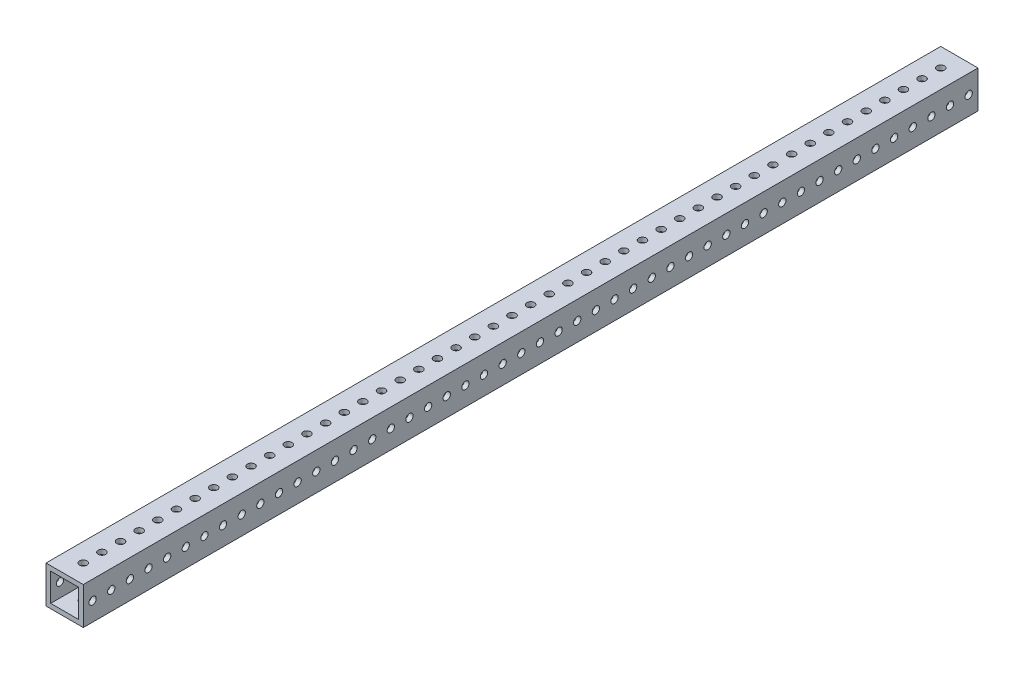
SolidWorks part; units mm, degrees
material "6061-T6 (SS)"
ref_plane "Front Plane" through (0, 0, 0) normal (0, 0, 1) x (1, 0, 0)
ref_plane "Top Plane" through (0, 0, 0) normal (0, 1, 0) x (1, 0, 0)
ref_plane "Right Plane" through (0, 0, 0) normal (1, 0, 0) x (0, 0, -1)
sketch "Sketch1" plane through (0, 0, 0) normal (0, 0, 1) x (1, 0, 0)
  line L0 (-9.525, 9.525) -> (9.525, 9.525)
  line L1 (-12.7, 12.7) -> (12.7, 12.7)
  line L2 (-12.7, 12.7) -> (-12.7, -12.7)
  line L3 (-12.7, -12.7) -> (12.7, -12.7)
  line L4 (12.7, 12.7) -> (12.7, -12.7)
  line L5 (9.525, 9.525) -> (9.525, -9.525)
  line L6 (-9.525, -9.525) -> (9.525, -9.525)
  line L7 (-9.525, 9.525) -> (-9.525, -9.525)
  line L8 (-12.7, 12.7) -> (12.7, -12.7) construction
  line L9 (12.7, 12.7) -> (-12.7, -12.7) construction
  point P5 (0, 0)
  dimension "D1" = 25.4
  dimension "D2" = 25.4
  dimension "D3" = 3.175
extrude "Boss-Extrude1" add sketch "Sketch1" along normal mid plane 609.6
sketch "Sketch2" plane through (0, 12.7, 0) normal (0, 1, 0) x (1, 0, 0)
  line L0 (12.7, -304.8) -> (-12.7, -304.8) construction
  line L1 (-12.7, -304.8) -> (-12.7, 304.8) construction
  line L4 (12.7, 304.8) -> (-12.7, 304.8) construction
  circle A0 centre (12.7, -292.1) radius 2.5527 construction
  circle A1 centre (25.4, -292.1) radius 2.5527 construction
  circle A2 centre (0, -292.1) radius 2.5527
  circle A3 centre (0, -279.4) radius 2.5527
  circle A4 centre (12.7, -279.4) radius 2.5527 construction
  circle A5 centre (25.4, -279.4) radius 2.5527 construction
  circle A6 centre (0, -266.7) radius 2.5527
  circle A7 centre (12.7, -266.7) radius 2.5527 construction
  circle A8 centre (25.4, -266.7) radius 2.5527 construction
  circle A9 centre (0, -254) radius 2.5527
  circle A10 centre (12.7, -254) radius 2.5527 construction
  circle A11 centre (25.4, -254) radius 2.5527 construction
  circle A12 centre (0, -241.3) radius 2.5527
  circle A13 centre (12.7, -241.3) radius 2.5527 construction
  circle A14 centre (25.4, -241.3) radius 2.5527 construction
  circle A15 centre (0, -228.6) radius 2.5527
  circle A16 centre (12.7, -228.6) radius 2.5527 construction
  circle A17 centre (25.4, -228.6) radius 2.5527 construction
  circle A18 centre (0, -215.9) radius 2.5527
  circle A19 centre (12.7, -215.9) radius 2.5527 construction
  circle A20 centre (25.4, -215.9) radius 2.5527 construction
  circle A21 centre (0, -203.2) radius 2.5527
  circle A22 centre (12.7, -203.2) radius 2.5527 construction
  circle A23 centre (25.4, -203.2) radius 2.5527 construction
  circle A24 centre (0, -190.5) radius 2.5527
  circle A25 centre (12.7, -190.5) radius 2.5527 construction
  circle A26 centre (25.4, -190.5) radius 2.5527 construction
  circle A27 centre (0, -177.8) radius 2.5527
  circle A28 centre (12.7, -177.8) radius 2.5527 construction
  circle A29 centre (25.4, -177.8) radius 2.5527 construction
  circle A30 centre (0, -165.1) radius 2.5527
  circle A31 centre (12.7, -165.1) radius 2.5527 construction
  circle A32 centre (25.4, -165.1) radius 2.5527 construction
  circle A33 centre (0, -152.4) radius 2.5527
  circle A34 centre (12.7, -152.4) radius 2.5527 construction
  circle A35 centre (25.4, -152.4) radius 2.5527 construction
  circle A36 centre (0, -139.7) radius 2.5527
  circle A37 centre (12.7, -139.7) radius 2.5527 construction
  circle A38 centre (25.4, -139.7) radius 2.5527 construction
  circle A39 centre (0, -127) radius 2.5527
  circle A40 centre (12.7, -127) radius 2.5527 construction
  circle A41 centre (25.4, -127) radius 2.5527 construction
  circle A42 centre (0, -114.3) radius 2.5527
  circle A43 centre (12.7, -114.3) radius 2.5527 construction
  circle A44 centre (25.4, -114.3) radius 2.5527 construction
  circle A45 centre (0, -101.6) radius 2.5527
  circle A46 centre (12.7, -101.6) radius 2.5527 construction
  circle A47 centre (25.4, -101.6) radius 2.5527 construction
  circle A48 centre (0, -88.9) radius 2.5527
  circle A49 centre (12.7, -88.9) radius 2.5527 construction
  circle A50 centre (25.4, -88.9) radius 2.5527 construction
  circle A51 centre (0, -76.2) radius 2.5527
  circle A52 centre (12.7, -76.2) radius 2.5527 construction
  circle A53 centre (25.4, -76.2) radius 2.5527 construction
  circle A54 centre (0, -63.5) radius 2.5527
  circle A55 centre (12.7, -63.5) radius 2.5527 construction
  circle A56 centre (25.4, -63.5) radius 2.5527 construction
  circle A57 centre (0, -50.8) radius 2.5527
  circle A58 centre (12.7, -50.8) radius 2.5527 construction
  circle A59 centre (25.4, -50.8) radius 2.5527 construction
  circle A60 centre (0, -38.1) radius 2.5527
  circle A61 centre (12.7, -38.1) radius 2.5527 construction
  circle A62 centre (25.4, -38.1) radius 2.5527 construction
  circle A63 centre (0, -25.4) radius 2.5527
  circle A64 centre (12.7, -25.4) radius 2.5527 construction
  circle A65 centre (25.4, -25.4) radius 2.5527 construction
  circle A66 centre (0, -12.7) radius 2.5527
  circle A67 centre (12.7, -12.7) radius 2.5527 construction
  circle A68 centre (25.4, -12.7) radius 2.5527 construction
  circle A69 centre (0, 0) radius 2.5527
  circle A70 centre (12.7, 0) radius 2.5527 construction
  circle A71 centre (25.4, 0) radius 2.5527 construction
  circle A72 centre (0, 12.7) radius 2.5527
  circle A73 centre (12.7, 12.7) radius 2.5527 construction
  circle A74 centre (25.4, 12.7) radius 2.5527 construction
  circle A75 centre (0, 25.4) radius 2.5527
  circle A76 centre (12.7, 25.4) radius 2.5527 construction
  circle A77 centre (25.4, 25.4) radius 2.5527 construction
  circle A78 centre (0, 38.1) radius 2.5527
  circle A79 centre (12.7, 38.1) radius 2.5527 construction
  circle A80 centre (25.4, 38.1) radius 2.5527 construction
  circle A81 centre (0, 50.8) radius 2.5527
  circle A82 centre (12.7, 50.8) radius 2.5527 construction
  circle A83 centre (25.4, 50.8) radius 2.5527 construction
  circle A84 centre (0, 63.5) radius 2.5527
  circle A85 centre (12.7, 63.5) radius 2.5527 construction
  circle A86 centre (25.4, 63.5) radius 2.5527 construction
  circle A87 centre (0, 76.2) radius 2.5527
  circle A88 centre (12.7, 76.2) radius 2.5527 construction
  circle A89 centre (25.4, 76.2) radius 2.5527 construction
  circle A90 centre (0, 88.9) radius 2.5527
  circle A91 centre (12.7, 88.9) radius 2.5527 construction
  circle A92 centre (25.4, 88.9) radius 2.5527 construction
  circle A93 centre (0, 101.6) radius 2.5527
  circle A94 centre (12.7, 101.6) radius 2.5527 construction
  circle A95 centre (25.4, 101.6) radius 2.5527 construction
  circle A96 centre (0, 114.3) radius 2.5527
  circle A97 centre (12.7, 114.3) radius 2.5527 construction
  circle A98 centre (25.4, 114.3) radius 2.5527 construction
  circle A99 centre (0, 127) radius 2.5527
  circle A100 centre (12.7, 127) radius 2.5527 construction
  circle A101 centre (25.4, 127) radius 2.5527 construction
  circle A108 centre (0, 152.4) radius 2.5527 [skipped]
  circle A109 centre (12.7, 152.4) radius 2.5527 [skipped]
  circle A110 centre (25.4, 152.4) radius 2.5527 [skipped]
  circle A111 centre (0, 139.7) radius 2.5527 [skipped]
  circle A112 centre (12.7, 139.7) radius 2.5527 [skipped]
  circle A113 centre (25.4, 139.7) radius 2.5527 [skipped]
  circle A114 centre (25.4, 139.7) radius 2.5527 construction
  circle A115 centre (12.7, 139.7) radius 2.5527 construction
  circle A116 centre (0, 139.7) radius 2.5527
  circle A117 centre (25.4, 152.4) radius 2.5527 construction
  circle A118 centre (12.7, 152.4) radius 2.5527 construction
  circle A119 centre (0, 152.4) radius 2.5527
  circle A120 centre (25.4, 165.1) radius 2.5527 construction
  circle A121 centre (12.7, 165.1) radius 2.5527 construction
  circle A122 centre (0, 165.1) radius 2.5527
  circle A123 centre (25.4, 177.8) radius 2.5527 construction
  circle A124 centre (12.7, 177.8) radius 2.5527 construction
  circle A125 centre (0, 177.8) radius 2.5527
  circle A126 centre (25.4, 190.5) radius 2.5527 construction
  circle A127 centre (12.7, 190.5) radius 2.5527 construction
  circle A128 centre (0, 190.5) radius 2.5527
  circle A129 centre (25.4, 203.2) radius 2.5527 construction
  circle A130 centre (12.7, 203.2) radius 2.5527 construction
  circle A131 centre (0, 203.2) radius 2.5527
  circle A132 centre (25.4, 215.9) radius 2.5527 construction
  circle A133 centre (12.7, 215.9) radius 2.5527 construction
  circle A134 centre (0, 215.9) radius 2.5527
  circle A135 centre (25.4, 228.6) radius 2.5527 construction
  circle A136 centre (12.7, 228.6) radius 2.5527 construction
  circle A137 centre (0, 228.6) radius 2.5527
  circle A138 centre (25.4, 241.3) radius 2.5527 construction
  circle A139 centre (12.7, 241.3) radius 2.5527 construction
  circle A140 centre (0, 241.3) radius 2.5527
  circle A141 centre (25.4, 254) radius 2.5527 construction
  circle A142 centre (12.7, 254) radius 2.5527 construction
  circle A143 centre (0, 254) radius 2.5527
  circle A144 centre (25.4, 266.7) radius 2.5527 construction
  circle A145 centre (12.7, 266.7) radius 2.5527 construction
  circle A146 centre (0, 266.7) radius 2.5527
  circle A147 centre (25.4, 279.4) radius 2.5527 construction
  circle A148 centre (12.7, 279.4) radius 2.5527 construction
  circle A149 centre (0, 279.4) radius 2.5527
  circle A150 centre (25.4, 292.1) radius 2.5527 construction
  circle A151 centre (12.7, 292.1) radius 2.5527 construction
  circle A152 centre (0, 292.1) radius 2.5527
  dimension "D2" = 5.1054
  dimension "D4" = 12.7
  dimension "D1" = 12.7
  dimension "D3" = 25.4
  dimension "D6" = 12.7
  dimension "D7" = 177.8
  dimension "D5" = 36
  dimension "D8" = 14
extrude "Cut-Extrude1" cut sketch "Sketch2" against normal through all
sketch "Sketch4" plane through (12.7, 0, 0) normal (1, 0, 0) x (0, 0, -1)
  line L1 (-304.8, -12.7) -> (-304.8, 12.7) construction
  line L2 (-304.8, -12.7) -> (304.8, -12.7) construction
  circle A2 centre (-298.45, 0) radius 2.4892
  circle A3 centre (-285.75, 0) radius 2.4892
  circle A16 centre (-273.05, 0) radius 2.4892
  circle A17 centre (-260.35, 0) radius 2.4892
  circle A18 centre (-247.65, 0) radius 2.4892
  circle A19 centre (133.35, 0) radius 2.4892
  circle A20 centre (146.05, 0) radius 2.4892
  circle A21 centre (158.75, 0) radius 2.4892
  circle A22 centre (171.45, 0) radius 2.4892
  circle A23 centre (184.15, 0) radius 2.4892
  circle A24 centre (196.85, 0) radius 2.4892
  circle A25 centre (209.55, 0) radius 2.4892
  circle A26 centre (222.25, 0) radius 2.4892
  circle A27 centre (234.95, 0) radius 2.4892
  circle A28 centre (247.65, 0) radius 2.4892
  circle A29 centre (260.35, 0) radius 2.4892
  circle A30 centre (273.05, 0) radius 2.4892
  circle A31 centre (285.75, 0) radius 2.4892
  circle A32 centre (298.45, 0) radius 2.4892
  circle A35 centre (-234.95, 0) radius 2.4892
  circle A36 centre (-222.25, 0) radius 2.4892
  circle A37 centre (-209.55, 0) radius 2.4892
  circle A38 centre (-196.85, 0) radius 2.4892
  circle A39 centre (-184.15, 0) radius 2.4892
  circle A40 centre (-171.45, 0) radius 2.4892
  circle A41 centre (-158.75, 0) radius 2.4892
  circle A42 centre (-146.05, 0) radius 2.4892
  circle A43 centre (-133.35, 0) radius 2.4892
  circle A44 centre (-120.65, 0) radius 2.4892
  circle A45 centre (-107.95, 0) radius 2.4892
  circle A46 centre (-95.25, 0) radius 2.4892
  circle A47 centre (-82.55, 0) radius 2.4892
  circle A48 centre (-69.85, 0) radius 2.4892
  circle A49 centre (-57.15, 0) radius 2.4892
  circle A50 centre (-44.45, 0) radius 2.4892
  circle A51 centre (-31.75, 0) radius 2.4892
  circle A52 centre (-19.05, 0) radius 2.4892
  circle A53 centre (-6.35, 0) radius 2.4892
  circle A54 centre (6.35, 0) radius 2.4892
  circle A55 centre (19.05, 0) radius 2.4892
  circle A56 centre (31.75, 0) radius 2.4892
  circle A57 centre (44.45, 0) radius 2.4892
  circle A58 centre (57.15, 0) radius 2.4892
  circle A59 centre (69.85, 0) radius 2.4892
  circle A60 centre (82.55, 0) radius 2.4892
  circle A61 centre (95.25, 0) radius 2.4892
  circle A62 centre (107.95, 0) radius 2.4892
  circle A63 centre (120.65, 0) radius 2.4892
  dimension "D2" = 4.9784
  dimension "D1" = 6.35
  dimension "D3" = 12.7
  dimension "D4" = 12.7
  dimension "D5" = 34
  dimension "D6" = 10
  dimension "D7" = 6
extrude "Cut-Extrude3" cut sketch "Sketch4" against normal through all
